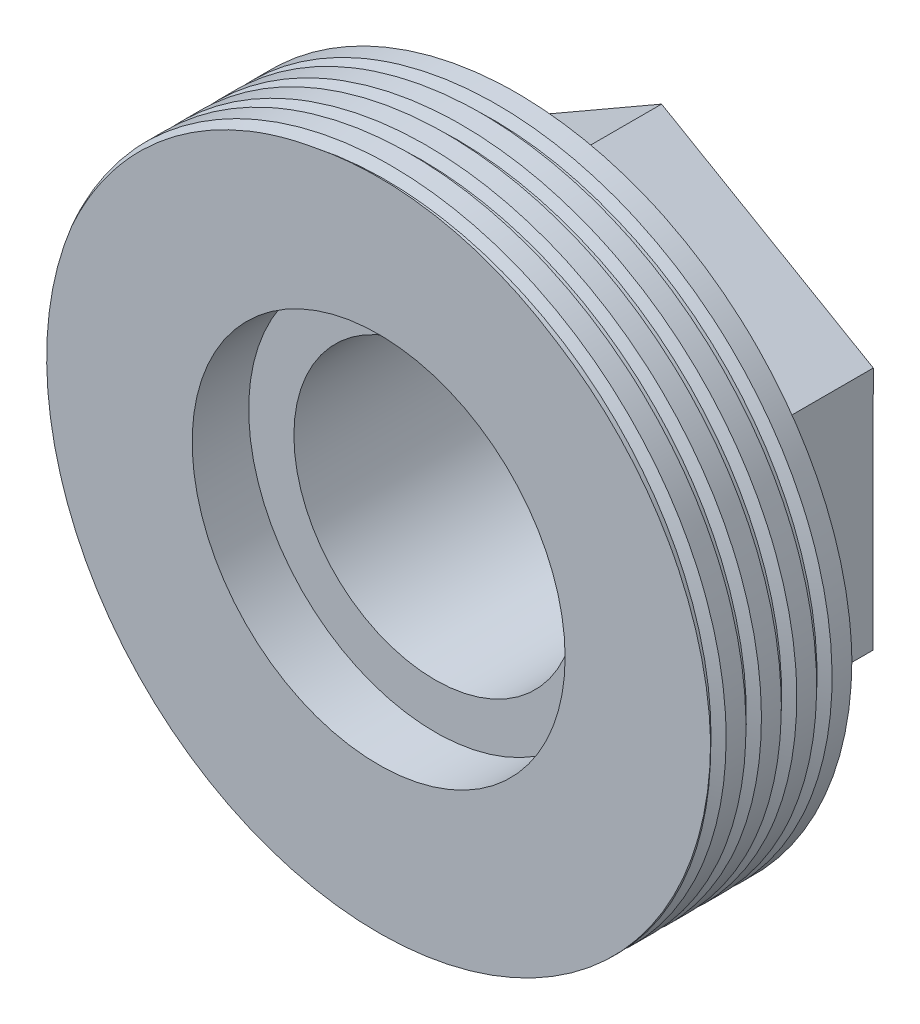
SolidWorks part; units mm, degrees
ref_plane "Front Plane" through (0, 0, 0) normal (0, 0, 1) x (1, 0, 0)
ref_plane "Top Plane" through (0, 0, 0) normal (0, 1, 0) x (1, 0, 0)
ref_plane "Right Plane" through (0, 0, 0) normal (1, 0, 0) x (0, 0, -1)
sketch "Sketch3" plane through (0, 0, 0) normal (0, 0, 1) x (1, 0, 0)
  circle A3 centre (8.3476, 27.7238) radius 14.9225
  dimension "D1" = 29.845
extrude "Boss-Extrude1" add sketch "Sketch3" against normal blind 12.7 contours A3 region at (8.3476, 27.7238, 0)
sketch "Sketch11" plane through (0, 0, 0) normal (0, 0, 1) x (1, 0, 0)
  circle A0 centre (8.3476, 27.7238) radius 6.35
  dimension "D1" = 12.7
extrude "Cut-Extrude3" cut sketch "Sketch11" against normal up to surface (12.7 mm away) up to face at (23.2701, 27.7238, -12.7)
sketch "Sketch12" plane through (0, 0, 0) normal (0, 0, 1) x (1, 0, 0)
  circle A1 centre (8.3476, 27.7238) radius 8.382
  dimension "D1" = 16.764
extrude "Cut-Extrude4" cut sketch "Sketch12" against normal blind 2.54
thread "Thread1" pitch 0.7937 method cut profile "Thread Profile1" start angle 0, offset 0.7937, length 7.62, pitch 1.5875, diameter 29.845
ref_plane "Plane1" through (-6.5749, 27.7238, 0.7937) normal (0, -1, 0) x (-1, 0, 0)
sketch "Thread Profile1" plane through (-6.5749, 27.7238, 0.7937) normal (0, -1, 0) x (-1, 0, 0)
  line L0 (0, 0) -> (0, 0.7937) construction
  line L11 (0, 0) -> (0, 0.6945)
  line L12 (0, 0.6945) -> (-0.4296, 0.4465)
  line L13 (-0.4296, 0.4465) -> (-0.4296, 0.248)
  line L15 (-0.4296, 0.248) -> (0, 0)
  line L17 (-0.4296, 0.3473) -> (0, 0.3473) construction
  point P2 (0, 0)
  dimension "Pitch" = 0.7937
  dimension "Profile_Angle" = 60
  dimension "Profile_Land" = 0.1984
  dimension "Profile_Height" = 0.4296
sketch "Sketch14" plane through (0, 0, -12.7) normal (0, 0, -1) x (-1, 0, 0)
  line L1 (1.1867, 22.2406) -> (1.1681, 33.2391)
  line L2 (1.1681, 33.2391) -> (-8.3661, 38.7223)
  line L3 (-8.3661, 38.7223) -> (-17.8818, 33.207)
  line L4 (-17.8818, 33.207) -> (-17.8633, 22.2085)
  line L5 (-17.8633, 22.2085) -> (-8.3291, 16.7253)
  line L6 (-8.3291, 16.7253) -> (1.1867, 22.2406)
  circle A0 centre (-8.3476, 27.7238) radius 9.525 construction
  circle A3 centre (-8.3476, 27.7238) radius 14.9225
  circle A4 centre (-8.3476, 27.7238) radius 14.9225
  dimension "D2" = 0
  dimension "D1" = 19.05
extrude "Cut-Extrude6" cut sketch "Sketch14" against normal blind 6.35
